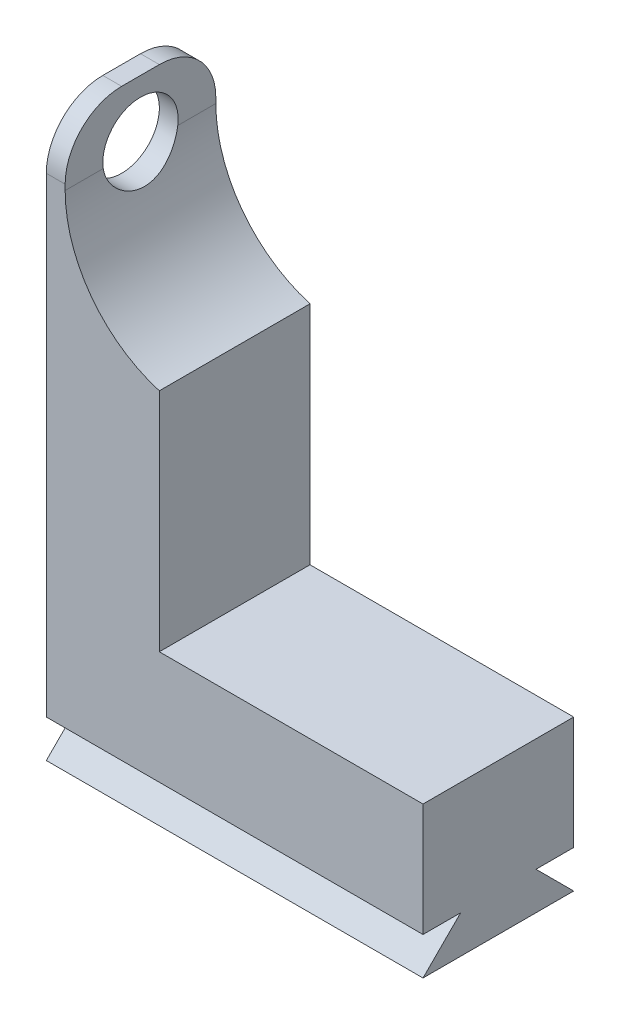
SolidWorks part; units mm, degrees
ref_plane "Front Plane" through (0, 0, 0) normal (0, 0, 1) x (1, 0, 0)
ref_plane "Top Plane" through (0, 0, 0) normal (0, 1, 0) x (1, 0, 0)
ref_plane "Right Plane" through (0, 0, 0) normal (1, 0, 0) x (0, 0, -1)
sketch "Sketch1" plane through (0, 0, 0) normal (1, 0, 0) x (0, 0, -1)
  line L1 (-4, -15) -> (4, -15)
  line L2 (-4, -15) -> (-4, 15)
  line L3 (-4, 15) -> (4, 15)
  line L4 (4, -15) -> (4, 15)
  line L5 (-4, -15) -> (4, 15) construction
  line L6 (-4, 15) -> (4, -15) construction
  point P0 (0, 0)
extrude "Boss-Extrude1" add sketch "Sketch1" along normal blind 6
sketch "Sketch2" plane through (6, 0, 0) normal (1, 0, 0) x (0, 0, -1)
  line L0 (-4, 15) -> (-4, -15) construction
  line L1 (4, 15) -> (-4, 15)
  line L2 (4, 15) -> (4, 5)
  line L3 (4, 5) -> (-4, 5)
  line L4 (-4, 15) -> (-4, 5)
extrude "Cut-Extrude1" cut sketch "Sketch2" against normal blind 5
sketch "Sketch3" plane through (0, 0, 0) normal (-1, 0, 0) x (0, 0, 1)
  line L0 (0, 15) -> (0, 12) construction
  line L1 (-4, 15) -> (4, 15) construction
  circle A0 centre (0, 12) radius 2
extrude "Cut-Extrude2" cut sketch "Sketch3" against normal up to next
fillet "Fillet1" radius 3 2 edges at (0.5, 15, -4) (0.5, 15, 4)
fillet "Fillet2" radius 7 1 edges at (1, 5, 0)
sketch "Sketch4" plane through (6, 0, 0) normal (1, 0, 0) x (0, 0, -1)
  line L0 (-4, 5) -> (-4, -15) construction
  line L1 (4, -15) -> (-4, -15)
  line L2 (4, -15) -> (4, -7)
  line L3 (4, -7) -> (-4, -7)
  line L4 (-4, -15) -> (-4, -7)
extrude "Boss-Extrude2" add sketch "Sketch4" along normal blind 14
sketch "Sketch6" plane through (0, 0, 0) normal (-1, 0, 0) x (0, 0, 1)
  line L0 (4, -15) -> (4, -13)
  line L1 (4, 12) -> (4, -15) construction
  line L2 (4, -13) -> (2, -13)
  line L3 (2, -13) -> (4, -15)
  line L4 (-4, -15) -> (-4, -13)
  line L5 (-4, -15) -> (-4, 12) construction
  line L6 (-4, -13) -> (-2, -13)
  line L7 (-2, -13) -> (-4, -15)
extrude "Cut-Extrude4" cut sketch "Sketch6" against normal up to next
